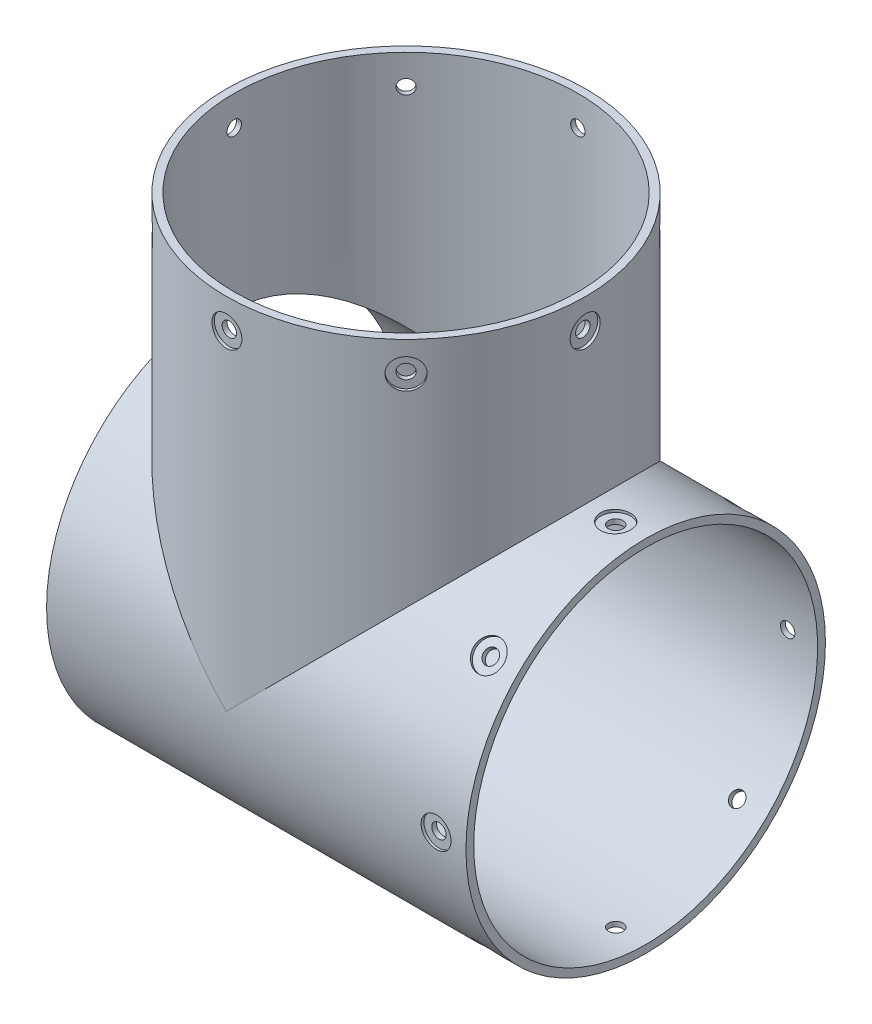
SolidWorks part; units mm, degrees
ref_plane "정면" through (0, 0, 0) normal (0, 0, 1) x (1, 0, 0)
ref_plane "윗면" through (0, 0, 0) normal (0, 1, 0) x (1, 0, 0)
ref_plane "우측면" through (0, 0, 0) normal (1, 0, 0) x (0, 0, -1)
sketch "스케치1" plane through (0, 0, 0) normal (0, 1, 0) x (1, 0, 0)
  circle A0 centre (0, 0) radius 30
  dimension "D1" = 60
extrude "보스-돌출1" add sketch "스케치1" along normal blind 60
sketch "스케치2" plane through (0, 0, 0) normal (1, 0, 0) x (0, 0, -1)
  line L0 (-30, 0) -> (30, 0) construction
  circle A0 centre (0, 0) radius 30
extrude "보스-돌출2" add sketch "스케치2" along normal blind 40 and the other way blind 30
sketch "스케치3" plane through (0, 60, 0) normal (0, 1, 0) x (1, 0, 0)
  circle A0 centre (0, 0) radius 28.7
  circle A1 centre (0, 0) radius 30 construction
  dimension "D1" = 1.3
extrude "컷-돌출1" cut sketch "스케치3" against normal blind 60
sketch "스케치4" plane through (-30, 0, 0) normal (-1, 0, 0) x (0, 0, 1)
  circle A0 centre (0, 0) radius 28.7
  circle A1 centre (0, 0) radius 30 construction
  dimension "D1" = 1.3
extrude "컷-돌출2" cut sketch "스케치4" against normal through all
ref_plane "평면1" through (0, 0, -30) normal (0, 0, -1) x (-1, 0, 0)
sketch "스케치5" plane through (0, 0, -30) normal (0, 0, -1) x (-1, 0, 0)
  line L0 (-40, 30) -> (-40, -30) construction
  point P0 (-35, 0)
  dimension "D1" = 5
hole_wizard "M2 남비 머리 나사용 카운터보어1" positions "스케치6" profile "스케치7" counterbore size "M2" standard "ISO"
sketch "스케치6" plane through (0, 0, -30) normal (0, 0, -1) x (-1, 0, 0)
  point P0 (-35, 0)
sketch "스케치7" plane through (35, 0, -30) normal (1, 0, 0) x (0, 1, 0)
  line L0 (0, 0) -> (0, 3.721)
  line L1 (0, 3.721) -> (1.2, 3)
  line L2 (1.2, 3) -> (1.2, 0.5)
  line L3 (1.2, 0.5) -> (2.5, 0.5)
  line L4 (2.5, 0.5) -> (2.5, 0)
  line L5 (2.5, 0) -> (0, 0)
  line L10 (0, 3.721) -> (-1.2, 3) construction
  line L11 (0, -6.35) -> (0, 107.95) construction
  dimension "구멍 지름" = 2.4
  dimension "구멍 깊이" = 3
  dimension "카운터보어 지름" = 5
  dimension "카운터보어 깊이" = 0.5
  dimension "드릴 각도" = 118
pattern_circular "원형 패턴1" count 8 over 360 about axis through (40, 0, 0) along (1, 0, 0) of "M2 남비 머리 나사용 카운터보어1"
ref_plane "평면2" through (30, 0, 0) normal (1, 0, 0) x (0, 0, -1)
sketch "스케치8" plane through (30, 0, 0) normal (1, 0, 0) x (0, 0, -1)
  line L0 (30, 60) -> (-30, 60) construction
  point P0 (0, 55)
  dimension "D1" = 5
hole_wizard "M2 남비 머리 나사용 카운터보어2" positions "스케치9" profile "스케치10" counterbore size "M2" standard "ISO"
sketch "스케치9" plane through (30, 0, 0) normal (1, 0, 0) x (0, 0, -1)
  point P0 (0, 55)
sketch "스케치10" plane through (30, 55, 0) normal (0, 1, 0) x (0, 0, -1)
  line L0 (0, 0) -> (0, 3.721)
  line L1 (0, 3.721) -> (1.2, 3)
  line L2 (1.2, 3) -> (1.2, 0.5)
  line L3 (1.2, 0.5) -> (2.5, 0.5)
  line L4 (2.5, 0.5) -> (2.5, 0)
  line L5 (2.5, 0) -> (0, 0)
  line L10 (0, 3.721) -> (-1.2, 3) construction
  line L11 (0, -6.35) -> (0, 107.95) construction
  dimension "구멍 지름" = 2.4
  dimension "구멍 깊이" = 3
  dimension "카운터보어 지름" = 5
  dimension "카운터보어 깊이" = 0.5
  dimension "드릴 각도" = 118
pattern_circular "원형 패턴2" count 8 over 360 about axis through (0, 60, 0) along (0, 1, 0) of "M2 남비 머리 나사용 카운터보어2"
